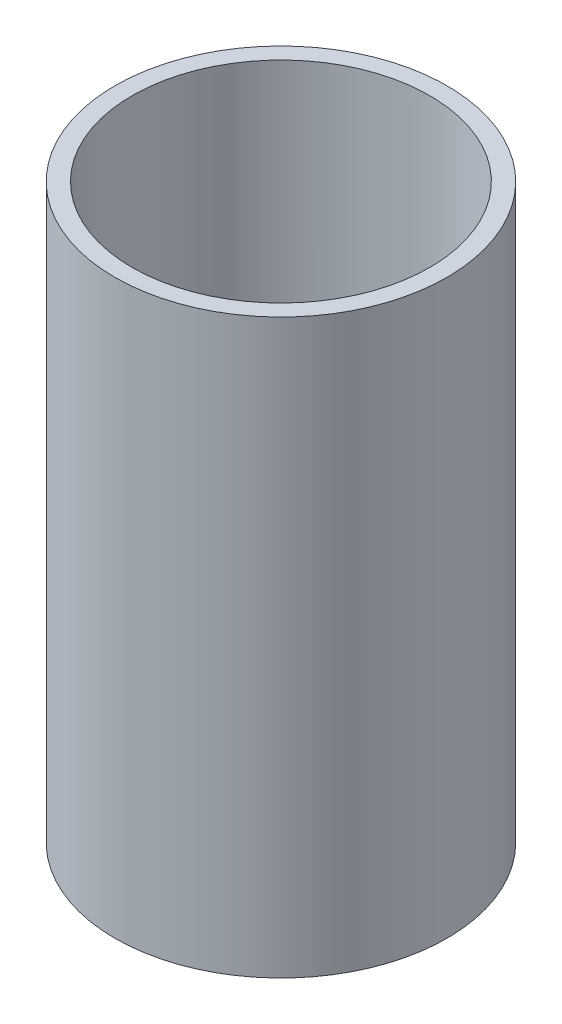
SolidWorks part; units mm, degrees
ref_plane "Front Plane" through (0, 0, 0) normal (0, 0, 1) x (1, 0, 0)
ref_plane "Top Plane" through (0, 0, 0) normal (0, 1, 0) x (1, 0, 0)
ref_plane "Right Plane" through (0, 0, 0) normal (1, 0, 0) x (0, 0, -1)
sketch "Sketch1" plane through (0, 0, 0) normal (0, 1, 0) x (1, 0, 0)
  circle A0 centre (0, 0) radius 2.6
  circle A1 centre (0, 0) radius 2.9
  dimension "D1" = 5.8
  dimension "D2" = 5.2
extrude "Boss-Extrude1" add sketch "Sketch1" along normal blind 10
sketch "Sketch2" plane through (0, 0, 0) normal (0, 0, 1) x (1, 0, 0)
  circle A0 centre (0, 4) radius 1.5
  dimension "D1" = 3
  dimension "D2" = 4
extrude "Cut-Extrude1" cut sketch "Sketch2" against normal blind 10
